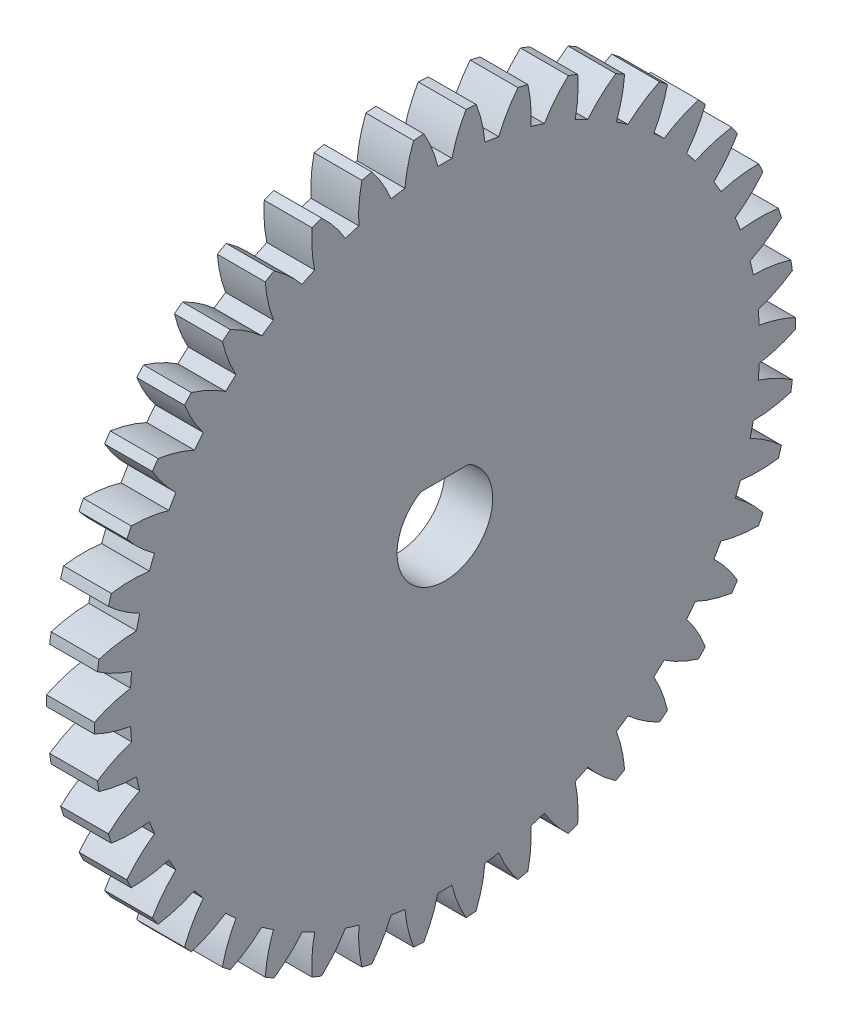
SolidWorks part; units mm, degrees
ref_plane "Plane1" through (0, 0, 0) normal (0, 0, 1) x (1, 0, 0)
ref_plane "Plane2" through (0, 0, 0) normal (0, 1, 0) x (1, 0, 0)
ref_plane "Plane3" through (0, 0, 0) normal (1, 0, 0) x (0, 0, -1)
other "Configuration Table"
sketch "HoldingSke" plane through (0, 0, 0) normal (0, 1, 0) x (1, 0, 0)
  line L0 (0, 0) -> (0.3716, -0.3346)
  line L1 (-15, 0) -> (100, 0) construction
  line L2 (0, 0) -> (-2.1039, 2.3779)
  line L3 (0, 0) -> (-11.863, 4.5341)
  line L4 (0, 0) -> (6.4178, 5.7786)
  line L5 (0, 0) -> (-46.8476, -17.4728)
  line L6 (0, 0) -> (-4.9738, -3.3558)
  line L7 (-2.1039, 2.3779) -> (8.6586, 51.2059)
  line L8 (-76.2, 54.61) -> (-73.9, 54.61)
  line L9 (-71.009, 38.7566) -> (-53.1078, 45.2721)
  line L10 (-76.2, 71.12) -> (104.1128, 71.12)
  line L11 (0, 0) -> (-6, 0)
  line L12 (-76.2, 101.6) -> (-76.133, 101.6)
  line L13 (24.9733, 27.94) -> (52.9518, 28.4284)
  line L14 (24.9733, 27.94) -> (24.9743, 27.94)
  line L15 (24.9733, 27.94) -> (100.4006, 29.5858)
  line L16 (-63.627, -2) -> (-12.827, -2)
  circle A0 centre (0, 0) radius 6
  circle A1 centre (0, 0) radius 37.5
  circle A2 centre (0, 0) radius 37.5
  circle A3 centre (0, 0) radius 6
  dimension "Num_teeth" = 42
  dimension "Pitch_radius" = 180.3128
  dimension "Width" = 6
  dimension "Thickness" = 6
sketch "BasProSke" plane through (0, 0, 0) normal (0, 1, 0) x (1, 0, 0)
  line L0 (-10, 0) -> (60, 0) construction
  line L1 (0, 0) -> (0, 44)
  line L2 (0, 0) -> (6, 0)
  line L3 (6, 0) -> (6, 44)
  line L4 (6, 44) -> (0, 44)
  dimension "Thickness" = 6
  dimension "Diameter" = 88
revolve "Base-Revolve" add sketch "BasProSke" angle 360 about L0
sketch "TooCutSke" plane through (0, 0, 0) normal (1, 0, 0) x (0, 0, -1)
  line L1 (0, 0) -> (0, 107) construction
  line L2 (0, 0) -> (-1.6877, 41.9661) construction
  line L3 (0, 0) -> (-6.2736, 83.715) construction
  line L4 (-1.6877, 41.9661) -> (-3.1368, 41.8575) construction
  arc A0 (0.8776, 39.4892) -> (-0.8776, 39.4892) centre (0, 0) ccw
  arc A1 (2.6666, 43.9446) -> (-2.6666, 43.9446) centre (0, 0) ccw
  circle A2 centre (0, 0) radius 42 construction
  circle A3 centre (0, 0) radius 39.4671 construction
  arc A4 (-0.8776, 39.4892) -> (-2.6666, 43.9446) centre (-17.2022, 35.5209) ccw
  arc A5 (2.6666, 43.9446) -> (0.8776, 39.4892) centre (17.2022, 35.5209) ccw
extrude "ToothCut" cut sketch "TooCutSke" along normal through all
fillet "Breaks" [suppressed] radius 0.04 tangent propagation no
fillet "RootFillets" [suppressed] radius 0.501
pattern_circular "TeethCuts" count 42 every 8.571 about axis through (-10, 0, 0) along (1, 0, 0) of "ToothCut", "RootFillets", "Breaks"
sketch "HubNeaOneSke" plane through (0, 0, 0) normal (-1, 0, 0) x (0, 0, 1)
  circle A0 centre (0, 0) radius 37.5
  dimension "Diameter" = 75
extrude "HubNearOne" [suppressed] add sketch "HubNeaOneSke" along normal blind 44.0001
sketch "HubNeaBotSke" plane through (0, 0, 0) normal (-1, 0, 0) x (0, 0, 1)
  circle A0 centre (0, 0) radius 37.5
  dimension "Diameter" = 75
extrude "HubNearBoth" [suppressed] add sketch "HubNeaBotSke" along normal blind 22
ref_plane "FarPln" through (6, 0, 0) normal (1, 0, 0) x (0, 0, -1)
sketch "HubFarSke" plane through (6, 0, 0) normal (1, 0, 0) x (0, 0, -1)
  circle A0 centre (0, 0) radius 37.5
  dimension "Diameter" = 75
extrude "HubFar" [suppressed] add sketch "HubFarSke" along normal blind 22
sketch "BorSke" plane through (0, 0, 0) normal (1, 0, 0) x (0, 0, -1)
  circle A0 centre (0, 0) radius 6
  dimension "Diameter" = 12
extrude "Bore" cut sketch "BorSke" along normal mid plane 100.0001
sketch "KeySke" plane through (0, 0, 0) normal (1, 0, 0) x (0, 0, -1)
  line L0 (-2.5, 0) -> (-2.5, 8.3)
  line L1 (-2.5, 8.3) -> (2.5, 8.3)
  line L2 (2.5, 8.3) -> (2.5, 0)
  line L3 (0, 0) -> (0, 34) construction
  line L4 (-2.5, 0) -> (2.5, 0)
  dimension "Width" = 5
extrude "Keyway" [suppressed] cut sketch "KeySke" along normal mid plane 100.0001
pattern_circular "Keyway2" [suppressed] count 2 every 90 about axis through (-10, 0, 0) along (1, 0, 0)
sketch "Sketch1" plane through (6, 0, 0) normal (1, 0, 0) x (0, 0, -1)
  line L0 (3, 5.1962) -> (-3, 5.1962)
  circle A0 centre (0, 0) radius 6 construction
  circle A1 centre (0, 0) radius 6
  circle A2 centre (0, 0) radius 6
  arc A3 (-3, 5.1962) -> (3, 5.1962) centre (0, 0) ccw
  dimension "D1" = 6
  dimension "D2" = 0
extrude "Boss-Extrude2" add sketch "Sketch1" against normal up to surface (6 mm away) contours L0 A1 region at (6, 5.5196, 0) up to face at (0, 0, -6)
equation "' \"Module@HoldingSke\" = 6.35"
equation "' \"Num_teeth@HoldingSke\" = 12"
equation "' \"Ap@HoldingSke\" =  20"
equation "' \"Ap@HoldingSke\" = 20"
equation "' \"Width@HoldingSke\" = 0.5 * 25.4"
equation "' \"Hub_dia@HoldingSke\"= 1 * 25.4"
equation "' \"Hub_dia@HoldingSke\" = 1 * 25.4"
equation "' \"Overall_len@HoldingSke\" = 1.0 * 25.4"
equation "' \"Bore@HoldingSke\" = 0.75 * 25.4"
equation "' \"T_dim@HoldingSke\" = 0.1 * 25.4"
equation "' \"Width@KeySke\" = 0.25 * 25.4"
equation "' \"Show_teeth@HoldingSke\" = 13"
equation "' \"Backlash@HoldingSke\" = 0.009 * 25.4"
equation "' \"Addendum_fac@HoldingSke\" = 1.0"
equation "' \"Dedendum_fac@HoldingSke\" = 1.25"
equation "' \"Dedendum_add@HoldingSke\" = 0.00005 * 25.4"
equation "' \"Clearance_fac@HoldingSke\" = 0.25"
equation "\"Pitch@HoldingSke\" = 1 / \"Module@HoldingSke\""
equation "\"Overcut_dia@TooCutSke\" = (\"Num_teeth@HoldingSke\" + 2 * \"Addendum_fac@HoldingSke\") / \"Pitch@HoldingSke\" + 0.002 * 25.4"
equation "\"Pitch_dia@TooCutSke\" = \"Num_teeth@HoldingSke\" / \"Pitch@HoldingSke\""
equation "\"Base_dia@TooCutSke\" = \"Num_teeth@HoldingSke\" / \"Pitch@HoldingSke\" * cos((\"Ap@HoldingSke\"  * 3.14159265 / 180))"
equation "\"Root_dia@TooCutSke\" = (\"Num_teeth@HoldingSke\" + 2) / \"Pitch@HoldingSke\" - 2 * (\"Addendum_fac@HoldingSke\" + \"Dedendum_fac@HoldingSke\") / \"Pitch@HoldingSke\" - \"Dedendum_add@HoldingSke\" * 2"
equation "\"Half_ang@TooCutSke\" = 180 / \"Num_teeth@HoldingSke\""
equation "\"Half_CT@TooCutSke\" = \"Num_teeth@HoldingSke\" / \"Pitch@HoldingSke\" * sin((3.14159265 / 2 / \"Num_teeth@HoldingSke\")) / 2 - 7 * \"Backlash@HoldingSke\" / 4"
equation "\"Flank_rad@TooCutSke\" = \"Num_teeth@HoldingSke\" / \"Pitch@HoldingSke\" / 5"
equation "\"Radius@RootFillets\" = \"Clearance_fac@HoldingSke\" / \"Pitch@HoldingSke\" + \"Dedendum_add@HoldingSke\""
equation "\"Break_rad@Breaks\" = 0.02 / \"Pitch@HoldingSke\""
equation "\"Thickness@HoldingSke\" = \"Width@HoldingSke\""
equation "\"OAL@HoldingSke\" = \"Thickness@HoldingSke\""
equation "\"MHD@HoldingSke\" = (\"Num_teeth@HoldingSke\" + 2) / \"Pitch@HoldingSke\" - 2 * (\"Addendum_fac@HoldingSke\" + \"Dedendum_fac@HoldingSke\")  / \"Pitch@HoldingSke\" - \"Dedendum_add@HoldingSke\" * 2"
equation "\"MBD@HoldingSke\" = (\"Num_teeth@HoldingSke\" + 2) / \"Pitch@HoldingSke\" - 2 * (\"Addendum_fac@HoldingSke\" + \"Dedendum_fac@HoldingSke\")  / \"Pitch@HoldingSke\" - \"Dedendum_add@HoldingSke\" * 2 - 0.002 * 25.4"
equation "\"MHD@HoldingSke\" = ((sgn( \"MHD@HoldingSke\" - \"Hub_dia@HoldingSke\" )-1)*( \"MHD@HoldingSke\" - \"Hub_dia@HoldingSke\" ))/-2+ \"Hub_dia@HoldingSke\""
equation "\"MBD@HoldingSke\" = ((sgn( \"MBD@HoldingSke\" - \"Bore@HoldingSke\" )-1)*( \"MBD@HoldingSke\" - \"Bore@HoldingSke\" ))/-2+ \"Bore@HoldingSke\""
equation "\"OAL@HoldingSke\" = ((sgn( \"OAL@HoldingSke\" - \"Overall_len@HoldingSke\" )+1)*( \"OAL@HoldingSke\" - \"Overall_len@HoldingSke\" ))/2 + \"Overall_len@HoldingSke\" + 0.000002 * 25.4"
equation "\"Num_teeth@TeethCuts\" = int( \"Show_teeth@HoldingSke\" ) + 1"
equation "\"Num_teeth@TeethCuts\" = ((sgn( \"Num_teeth@TeethCuts\" - \"Num_teeth@HoldingSke\" )-1)*( \"Num_teeth@TeethCuts\" - \"Num_teeth@HoldingSke\" ))/-2+ \"Num_teeth@HoldingSke\""
equation "\"Num_teeth@TeethCuts\" = ((sgn( \"Num_teeth@TeethCuts\" - 2.0)+1)*( \"Num_teeth@TeethCuts\" - 2.0))/2 +2.0"
equation "\"Angle@TeethCuts\" = 360.0 / \"Num_teeth@HoldingSke\""
equation "\"Diameter@BasProSke\" = (\"Num_teeth@HoldingSke\" + 2 * \"Addendum_fac@HoldingSke\") / \"Pitch@HoldingSke\""
equation "\"Thickness@BasProSke\"  = \"Thickness@HoldingSke\""
equation "' \"Fillet_rad@BasProSke\" =  \"Thickness@HoldingSke\" * 0.05"
equation "' \"Fillet_rad@BasProSke\" = \"Thickness@HoldingSke\" * 0.05"
equation "\"MHD@HoldingSke\" = ((sgn( \"MHD@HoldingSke\" - \"Root_dia@TooCutSke\" )-1)*( \"MHD@HoldingSke\" - \"Root_dia@TooCutSke\" ))/-2+ \"Root_dia@TooCutSke\""
equation "\"Diameter@HubNeaOneSke\" = \"MHD@HoldingSke\""
equation "\"Length@HubNearOne\" = \"OAL@HoldingSke\" - \"Thickness@BasProSke\""
equation "\"Diameter@HubNeaBotSke\" = \"MHD@HoldingSke\""
equation "\"Length@HubNearBoth\" = ( \"OAL@HoldingSke\" - \"Thickness@BasProSke\" ) / 2.0"
equation "\"Thickness@FarPln\" = \"Thickness@BasProSke\""
equation "\"Diameter@HubFarSke\" = \"MHD@HoldingSke\""
equation "\"Length@HubFar\" = ( \"OAL@HoldingSke\" - \"Thickness@BasProSke\" ) / 2.0"
equation "\"Diameter@BorSke\" = \"MBD@HoldingSke\""
equation "\"D1@Bore\" = \"OAL@HoldingSke\" * 2.0"
equation "\"D1@Keyway\" = \"OAL@HoldingSke\" * 2.0"
equation "\"Offset@KeySke\" = \"T_dim@HoldingSke\" + \"MBD@HoldingSke\" / 2.0"
